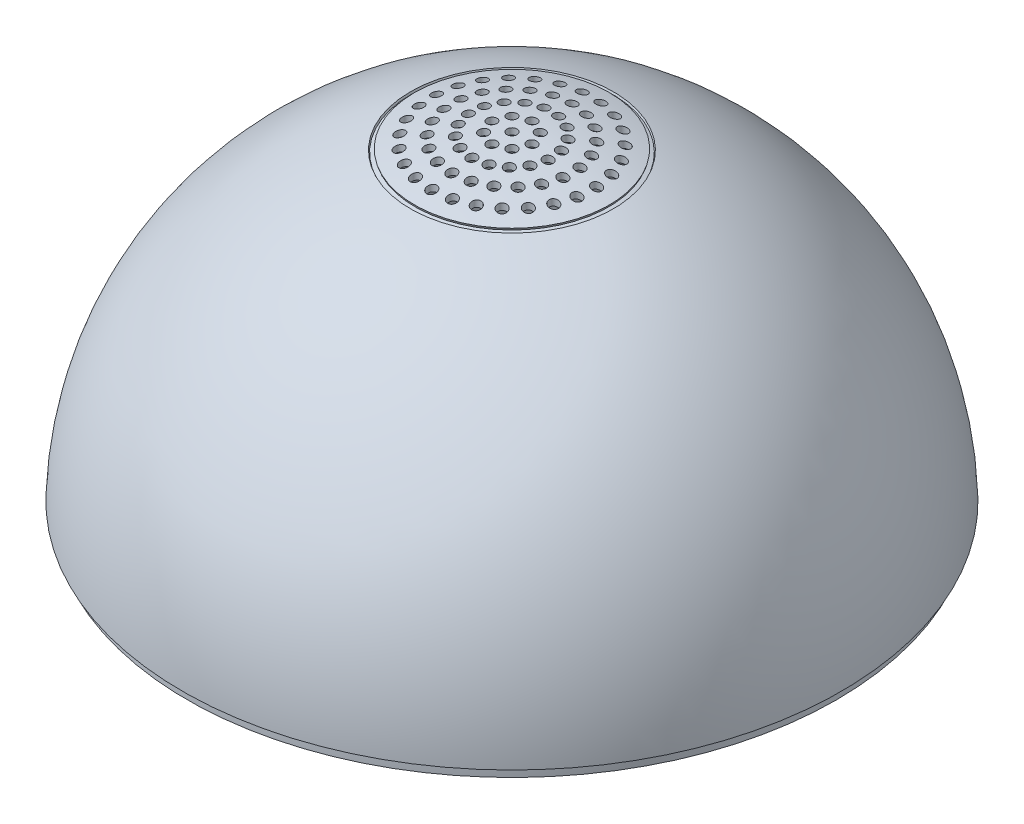
SolidWorks part; units mm, degrees
ref_plane "Front Plane" through (0, 0, 0) normal (0, 0, 1) x (1, 0, 0)
ref_plane "Top Plane" through (0, 0, 0) normal (0, 1, 0) x (1, 0, 0)
ref_plane "Right Plane" through (0, 0, 0) normal (1, 0, 0) x (0, 0, -1)
sketch "Sketch4" plane through (0, 0, 0) normal (0, 0, 1) x (1, 0, 0)
  line L0 (0, 82.288) -> (0, 79.75)
  line L1 (82.25, 0) -> (79.75, 0)
  line L2 (0, -82.25) -> (0, -79.75)
  line L3 (-82.25, 2.5) -> (-80.9614, 2.5)
  line L4 (-79.75, 0) -> (-81, 0)
  arc A1 (-80.9614, 2.5) -> (-81, 0) centre (0, 0) ccw
  arc A3 (-79.75, 0) -> (0, 79.75) centre (0, 0) cw
  arc A4 (-82.25, 2.5) -> (0, 82.288) centre (0, 0) cw
  dimension "D2" = 162
revolve "Revolve1" add sketch "Sketch4" angle 360 about L2 region at (-1.1635, 81.019, 0)
sketch "Sketch7" plane through (0, 0, 0) normal (0, 1, 0) x (1, 0, 0)
  circle A0 centre (-77.5, 0) radius 2
  circle A1 centre (77.5, 0) radius 2
  dimension "D1" = 4
  dimension "D2" = 4
  dimension "D3" = 77.5
  dimension "D4" = 77.5
extrude "Boss-Extrude2" add sketch "Sketch7" against normal blind 10 and the other way up to surface other way up to face at (79.75, 0, 0)
sketch "Sketch9" plane through (0, 0, 0) normal (0, 0, 1) x (1, 0, 0)
  line L0 (-25.6173, 79.0232) -> (-25.132, 77.8159)
  line L1 (0, 82.4131) -> (0, 81.7736)
  line L2 (-26.2955, 76.3133) -> (-25.2993, 71.2683)
  line L3 (0, 80.7167) -> (0, 75.6255)
  line L4 (-24.5385, 79.3648) -> (-24.155, 78.1247)
  arc A0 (-24.5385, 79.3648) -> (-25.6173, 79.0232) centre (0, 0) ccw
  arc A1 (-24.155, 78.1247) -> (-25.132, 77.8159) centre (0, 0) ccw
  arc A2 (0, 75.6255) -> (-25.2993, 71.2683) centre (0, 0) ccw
  arc A3 (0, 80.7167) -> (-26.2955, 76.3133) centre (0, 0) ccw
revolve "Cut-Revolve1" cut sketch "Sketch9" angle 360 about L1
sketch "Sketch12" plane through (0, 0, 0) normal (0, 1, 0) x (1, 0, 0)
  line L0 (0, 0) -> (0, -24.3494)
  circle A1 centre (0, 0) radius 1.25
  circle A2 centre (0, -20) radius 1.25
  circle A3 centre (0, -5) radius 1.25
  circle A4 centre (0, -15) radius 1.25
  circle A5 centre (0, -10) radius 1.25
  circle A6 centre (-3.5355, -3.5355) radius 1.25
  circle A7 centre (-5, 0) radius 1.25
  circle A8 centre (-3.5355, 3.5355) radius 1.25
  circle A9 centre (0, 5) radius 1.25
  circle A10 centre (3.5355, 3.5355) radius 1.25
  circle A11 centre (5, 0) radius 1.25
  circle A12 centre (3.5355, -3.5355) radius 1.25
  circle A13 centre (-5.4064, -8.4125) radius 1.25
  circle A14 centre (-9.0963, -4.1542) radius 1.25
  circle A15 centre (-9.8982, 1.4231) radius 1.25
  circle A16 centre (-7.5575, 6.5486) radius 1.25
  circle A17 centre (-2.8173, 9.5949) radius 1.25
  circle A18 centre (2.8173, 9.5949) radius 1.25
  circle A19 centre (7.5575, 6.5486) radius 1.25
  circle A20 centre (9.8982, 1.4231) radius 1.25
  circle A21 centre (9.0963, -4.1542) radius 1.25
  circle A22 centre (5.4064, -8.4125) radius 1.25
  circle A23 centre (-5.4186, -13.9871) radius 1.25
  circle A24 centre (-10.1054, -11.0851) radius 1.25
  circle A25 centre (-13.4274, -6.6861) radius 1.25
  circle A26 centre (-14.936, -1.384) radius 1.25
  circle A27 centre (-14.4274, 4.1049) radius 1.25
  circle A28 centre (-11.9703, 9.0395) radius 1.25
  circle A29 centre (-7.8965, 12.7533) radius 1.25
  circle A30 centre (-2.7562, 14.7446) radius 1.25
  circle A31 centre (2.7562, 14.7446) radius 1.25
  circle A32 centre (7.8965, 12.7533) radius 1.25
  circle A33 centre (11.9703, 9.0395) radius 1.25
  circle A34 centre (14.4274, 4.1049) radius 1.25
  circle A35 centre (14.936, -1.384) radius 1.25
  circle A36 centre (-6.1803, -19.0211) radius 1.25
  circle A37 centre (-11.7557, -16.1803) radius 1.25
  circle A38 centre (-16.1803, -11.7557) radius 1.25
  circle A39 centre (-19.0211, -6.1803) radius 1.25
  circle A40 centre (-20, 0) radius 1.25
  circle A41 centre (-19.0211, 6.1803) radius 1.25
  circle A42 centre (-16.1803, 11.7557) radius 1.25
  circle A43 centre (-11.7557, 16.1803) radius 1.25
  circle A44 centre (-6.1803, 19.0211) radius 1.25
  circle A45 centre (0, 20) radius 1.25
  circle A46 centre (6.1803, 19.0211) radius 1.25
  circle A47 centre (11.7557, 16.1803) radius 1.25
  circle A48 centre (16.1803, 11.7557) radius 1.25
  circle A49 centre (19.0211, 6.1803) radius 1.25
  circle A50 centre (20, 0) radius 1.25
  circle A51 centre (19.0211, -6.1803) radius 1.25
  circle A52 centre (16.1803, -11.7557) radius 1.25
  circle A53 centre (11.7557, -16.1803) radius 1.25
  circle A54 centre (6.1803, -19.0211) radius 1.25
  circle A55 centre (13.4274, -6.6861) radius 1.25
  circle A56 centre (10.1054, -11.0851) radius 1.25
  circle A57 centre (5.4186, -13.9871) radius 1.25
  point P29 (0, 0)
  point P50 (0, 0)
  point P77 (0, 0)
  point P116 (0, 0)
  dimension "D1" = 2.5
  dimension "D2" = 2.5
  dimension "D3" = 2.5
  dimension "D4" = 2.5
  dimension "D5" = 2.5
  dimension "D6" = 5
  dimension "D7" = 5
  dimension "D8" = 5
  dimension "D9" = 5
  dimension "D10" = 8
  dimension "D11" = 11
  dimension "D12" = 17
  dimension "D13" = 20
extrude "Cut-Extrude2" cut sketch "Sketch12" against normal through all both and the other way through all contours A1
extrude "Cut-Extrude3" cut sketch "Sketch12<12>" against normal through all both and the other way through all contours A3
sketch "Sketch12<12>" plane through (0, 0, 0) normal (0, 1, 0) x (1, 0, 0) same geometry as "Sketch12"
pattern_circular "CirPattern1" count 8 over 360 about axis through (0, 80.707, 0) along (0, 1, 0) of "Cut-Extrude3"
extrude "Cut-Extrude4" cut sketch "Sketch12<13>" against normal through all both and the other way through all contours A5
sketch "Sketch12<13>" plane through (0, 0, 0) normal (0, 1, 0) x (1, 0, 0) same geometry as "Sketch12"
extrude "Cut-Extrude6" cut sketch "Sketch12<15>" against normal through all both and the other way through all contours A2
sketch "Sketch12<15>" plane through (0, 0, 0) normal (0, 1, 0) x (1, 0, 0) same geometry as "Sketch12"
pattern_circular "CirPattern2" count 27 over 360 about axis through (0, 80.707, 0) along (0, 1, 0) of "Cut-Extrude6"
pattern_circular "CirPattern3" count 17 over 360 about axis through (0, 80.707, 0) along (0, 1, 0) of "Cut-Extrude4"
extrude "Cut-Extrude7" cut sketch "Sketch12<16>" against normal through all both and the other way through all contours A4
sketch "Sketch12<16>" plane through (0, 0, 0) normal (0, 1, 0) x (1, 0, 0) same geometry as "Sketch12"
pattern_circular "CirPattern4" count 22 over 360 about axis through (0, 80.707, 0) along (0, 1, 0) of "Cut-Extrude7"
sketch "Sketch13" plane through (0, -10, 0) normal (0, -1, 0) x (1, 0, 0)
  circle A0 centre (-77.5, 0) radius 2
  circle A1 centre (77.5, 0) radius 2
extrude "Cut-Extrude8" cut sketch "Sketch13" against normal up to surface (28.7033 mm away) body kept at (-82.25, 2.5, 0) up to face at (0, 75.3559, -26.1065)
